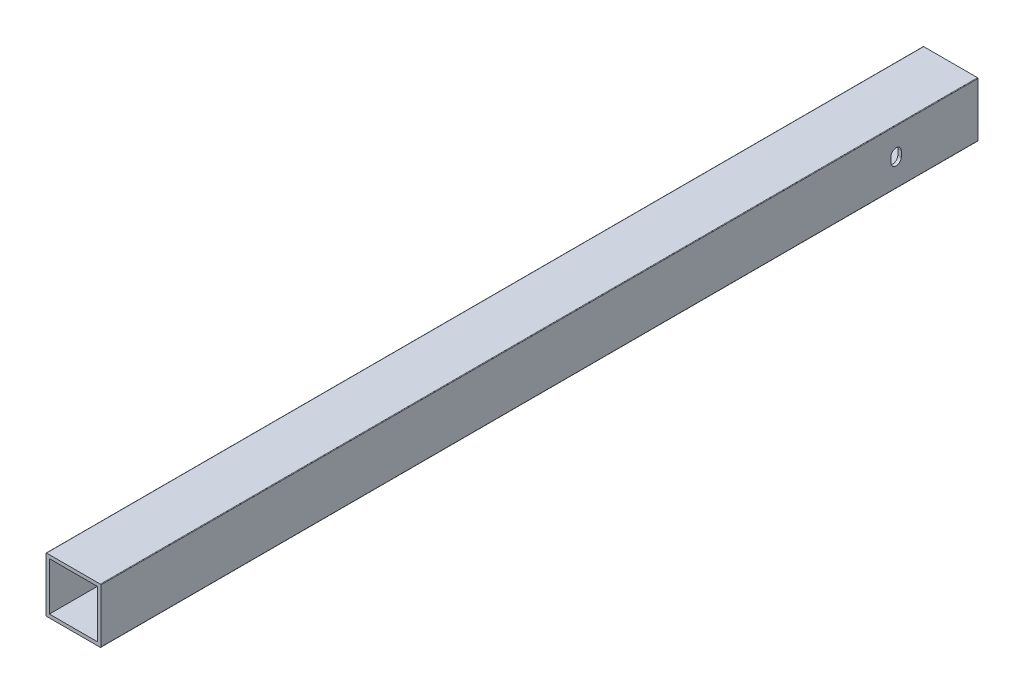
SolidWorks part; units mm, degrees
material "1060 Alloy"
ref_plane "Front Plane" through (0, 0, 0) normal (0, 0, 1) x (1, 0, 0)
ref_plane "Top Plane" through (0, 0, 0) normal (0, 1, 0) x (1, 0, 0)
ref_plane "Right Plane" through (0, 0, 0) normal (1, 0, 0) x (0, 0, -1)
ref_plane "Plane1" through (0, 0, 0) normal (0, 0, -1) x (-1, 0, 0)
sketch "Sketch1" plane through (0, 0, 0) normal (0, 0, -1) x (-1, 0, 0)
  line L4 (1.5875, -1.3335) -> (1.5875, 23.5585)
  line L5 (1.3335, 23.8125) -> (-23.5585, 23.8125)
  line L6 (-23.8125, 23.5585) -> (-23.8125, -1.3335)
  line L7 (-23.5585, -1.5875) -> (1.3335, -1.5875)
  line L9 (0, 22.225) -> (-22.225, 22.225)
  line L10 (0, 22.225) -> (0, 0)
  line L11 (0, 0) -> (-22.225, 0)
  line L12 (-22.225, 22.225) -> (-22.225, 0)
  line L13 (0, 22.225) -> (-22.225, 0) construction
  line L14 (0, 0) -> (-22.225, 22.225) construction
  arc A4 (1.3335, -1.5875) -> (1.5875, -1.3335) centre (1.3335, -1.3335) ccw
  arc A5 (1.5875, 23.5585) -> (1.3335, 23.8125) centre (1.3335, 23.5585) ccw
  arc A6 (-23.5585, 23.8125) -> (-23.8125, 23.5585) centre (-23.5585, 23.5585) ccw
  arc A7 (-23.8125, -1.3335) -> (-23.5585, -1.5875) centre (-23.5585, -1.3335) ccw
  point P24 (-11.1125, 11.1125)
  dimension "D1" = 25.4
  dimension "D2" = 25.4
  dimension "D3" = 1.5875
  dimension "D4" = 1.5875
  dimension "D5" = 1.5875
extrude "Boss-Extrude1" add sketch "Sketch1" against normal blind 406.4
sketch "Sketch2" plane through (-1.5875, 0, 0) normal (-1, 0, 0) x (0, 0, 1)
  line L0 (0, -1.3335) -> (0, 23.5585) construction
  line L1 (406.4, -1.3335) -> (0, -1.3335) construction
  line L2 (406.4, -1.3335) -> (406.4, 23.5585) construction
  circle A0 centre (12.6975, 11.3665) radius 1.5875
  circle A1 centre (393.7, 11.3665) radius 1.5875
  circle A2 centre (76.2, 11.3665) radius 6.35
  circle A3 centre (330.2, 11.3665) radius 6.35
  point P4 (0, 11.1125)
  dimension "D1" = 3.175
  dimension "D2" = 12.7
  dimension "D3" = 12.7
  dimension "D4" = 3.175
  dimension "D5" = 12.7
  dimension "D6" = 12.7
  dimension "D7" = 12.7
  dimension "D8" = 12.7
  dimension "D9" = 76.2
  dimension "D10" = 12.7
  dimension "D11" = 12.7
  dimension "D12" = 76.2
extrude "Cut-Extrude1" [suppressed] cut sketch "Sketch2" against normal through all
sketch "Sketch3" plane through (-1.5875, 0, 0) normal (-1, 0, 0) x (0, 0, 1)
  circle A0 centre (18.2509, 12.9013) radius 4.7907
sketch "Sketch4" plane through (23.8125, 0, 0) normal (1, 0, 0) x (0, 0, -1)
  line L2 (-40.3145, 9.8425) -> (-40.3145, 12.3825)
  line L4 (-35.552, 9.8425) -> (-35.552, 12.3825)
  line L6 (-40.3145, 12.3825) -> (-35.552, 12.3825)
  line L7 (-40.3145, 11.1125) -> (-35.552, 11.1125)
  line L8 (0, 23.5585) -> (0, -1.3335) construction
  line L9 (0, 11.1125) -> (-49.6378, 11.1125)
  circle A0 centre (-37.9333, 9.8425) radius 2.3812
  circle A1 centre (-37.9333, 12.3825) radius 2.3812
  dimension "D1" = 4.7625
  dimension "D2" = 37.9333
  dimension "D3" = 1.27
extrude "Cut-Extrude2" cut sketch "Sketch4" against normal through all contours L6 A1 | L6 A1 A0 | L9 A0 | L9 A1 | A1 A0 | A0 L4 L7 | A1 L7 L4 | A0 L7 L2 | A1 L2 L7 | A0 region at (23.8125, 9.1445, 37.9333) region at (23.8125, 10.8001, 40.2061) region at (23.8125, 11.4249, 40.2061) region at (23.8125, 10.8001, 35.6605) region at (23.8125, 11.5673, 37.9333) region at (23.8125, 11.7352, 40.1736) region at (23.8125, 10.6577, 37.9333) region at (23.8125, 13.3931, 37.9333) region at (23.8125, 11.4249, 35.6605)
